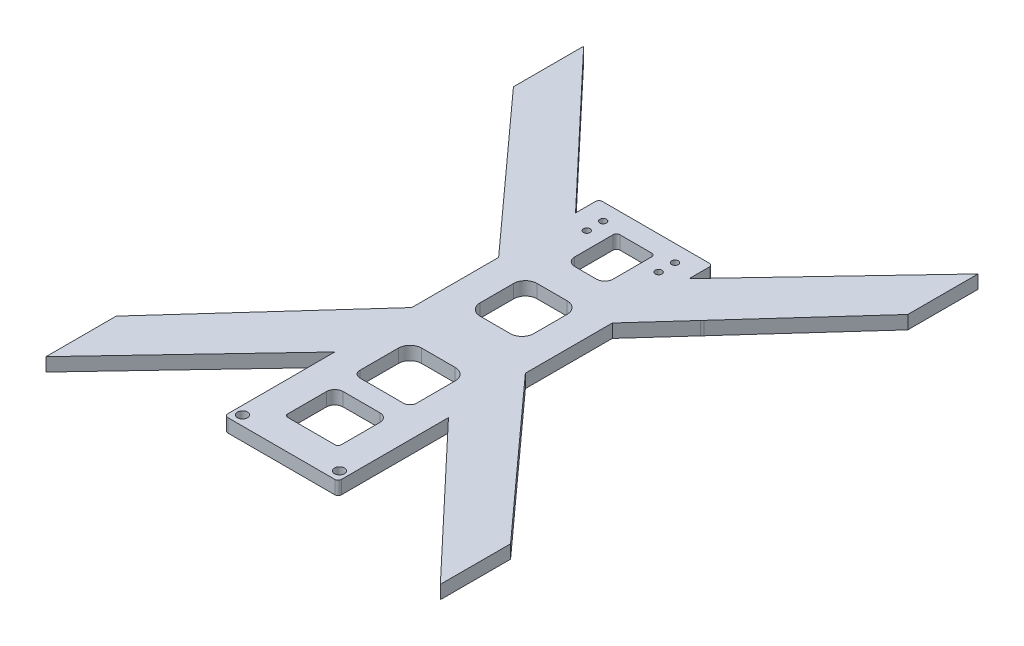
SolidWorks part; units mm, degrees
ref_plane "Front Plane" through (0, 0, 0) normal (0, 0, 1) x (1, 0, 0)
ref_plane "Top Plane" through (0, 0, 0) normal (0, 1, 0) x (1, 0, 0)
ref_plane "Right Plane" through (0, 0, 0) normal (1, 0, 0) x (0, 0, -1)
sketch "Frame Sketch" plane through (0, 0, 0) normal (0, 1, 0) x (1, 0, 0)
  line L0 (6.2981, 0.1404) -> (6.2981, 126.6085) construction
  line L6 (-48.6747, 0) -> (67.0859, 0) construction
  line L11 (6.2981, 0.1404) -> (6.2981, -105.8001) construction
  line L23 (-9.7019, 56.1404) -> (22.2981, 56.1404)
  line L24 (-10.7019, 55.1404) -> (-10.7019, -54.8596)
  line L25 (-9.7019, -55.8596) -> (22.2981, -55.8596)
  line L26 (23.2981, 55.1404) -> (23.2981, -54.8596)
  line L27 (-10.7019, 56.1404) -> (23.2981, -55.8596) construction
  line L28 (-10.7019, -55.8596) -> (23.2981, 56.1404) construction
  line L34 (23.2981, -22.8596) -> (65.2709, -67.262)
  line L37 (65.2709, -46.262) -> (65.2709, -67.262)
  line L38 (23.2981, 0.1404) -> (65.2709, -46.262)
  line L43 (23.2981, -22.8596) -> (23.2981, 0.1404)
  line L44 (-0.8423, -46.8596) -> (13.4385, -46.8596)
  line L45 (-1.7019, -46) -> (-1.7019, -34.3596)
  line L46 (0.7981, -31.8596) -> (11.7981, -31.8596)
  line L47 (14.2981, -46) -> (14.2981, -34.3596)
  line L48 (-1.7019, -46.8596) -> (14.2981, -31.8596) construction
  line L49 (-1.7019, -31.8596) -> (14.2981, -46.8596) construction
  line L50 (12.7981, -25.8596) -> (-0.2019, -25.8596)
  line L51 (14.7981, -23.8596) -> (14.7981, -12.3596)
  line L52 (11.2981, -8.8596) -> (1.2981, -8.8596)
  line L53 (-2.2019, -23.8596) -> (-2.2019, -12.3596)
  line L54 (14.7981, -25.8596) -> (-2.2019, -8.8596) construction
  line L55 (14.7981, -8.8596) -> (-2.2019, -25.8596) construction
  line L56 (1.7981, 8.1404) -> (10.7981, 8.1404)
  line L57 (-1.7019, 11.6404) -> (-1.7019, 21.6404)
  line L58 (1.7981, 25.1404) -> (10.7981, 25.1404)
  line L59 (14.2981, 11.6404) -> (14.2981, 21.6404)
  line L60 (-1.7019, 8.1404) -> (14.2981, 25.1404) construction
  line L61 (-1.7019, 25.1404) -> (14.2981, 8.1404) construction
  line L62 (3.0481, 35.1404) -> (9.5481, 35.1404)
  line L63 (0.5481, 37.6404) -> (0.5481, 49.1404)
  line L64 (1.5481, 50.1404) -> (11.0481, 50.1404)
  line L65 (12.0481, 37.6404) -> (12.0481, 49.1404)
  line L66 (0.5481, 35.1404) -> (12.0481, 50.1404) construction
  line L67 (0.5481, 50.1404) -> (12.0481, 35.1404) construction
  line L69 (23.2981, 49.1404) -> (65.2709, 93.5427)
  line L70 (23.2981, 26.1404) -> (65.2709, 72.5427)
  line L71 (65.2709, 72.5427) -> (65.2709, 93.5427)
  line L72 (23.2981, 26.1404) -> (23.2981, 49.1404)
  line L73 (-10.7019, 26.1404) -> (-52.6747, 72.5427)
  line L74 (-52.6747, 72.5427) -> (-52.6747, 93.5427)
  line L75 (-10.7019, 49.1404) -> (-52.6747, 93.5427)
  line L76 (-10.7019, 26.1404) -> (-10.7019, 49.1404)
  line L77 (-10.7019, -22.8596) -> (-52.6747, -67.262)
  line L78 (-52.6747, -46.262) -> (-52.6747, -67.262)
  line L79 (-10.7019, 0.1404) -> (-52.6747, -46.262)
  line L80 (-10.7019, -22.8596) -> (-10.7019, 0.1404)
  line L81 (-23.7019, 40.5123) -> (-10.7019, 26.1404)
  line L82 (-10.7019, 0.1404) -> (-23.7019, -14.2315)
  line L83 (-23.7019, 40.5123) -> (-10.7019, 26.1404)
  line L84 (-10.7019, 0.1404) -> (-23.7019, -14.2315)
  line L85 (-23.7019, 40.5123) -> (-10.7019, 26.1404)
  line L86 (-10.7019, 0.1404) -> (-23.7019, -14.2315)
  line L87 (-23.7019, 40.5123) -> (-10.7019, 26.1404)
  arc A8 (23.2981, 55.1404) -> (22.2981, 56.1404) centre (22.2981, 55.1404) ccw
  arc A9 (23.2981, -54.8596) -> (22.2981, -55.8596) centre (22.2981, -54.8596) cw
  arc A10 (-9.7019, 56.1404) -> (-10.7019, 55.1404) centre (-9.7019, 55.1404) ccw
  arc A11 (-9.7019, -55.8596) -> (-10.7019, -54.8596) centre (-9.7019, -54.8596) cw
  circle A12 centre (-8.2019, -52.9596) radius 1.5
  circle A13 centre (20.7981, -52.9596) radius 1.5
  arc A14 (14.2981, -46) -> (13.4385, -46.8596) centre (13.4385, -46) cw
  arc A15 (-0.8423, -46.8596) -> (-1.7019, -46) centre (-0.8423, -46) cw
  arc A16 (-1.7019, -34.3596) -> (0.7981, -31.8596) centre (0.7981, -34.3596) cw
  arc A17 (11.7981, -31.8596) -> (14.2981, -34.3596) centre (11.7981, -34.3596) cw
  arc A18 (14.7981, -23.8596) -> (12.7981, -25.8596) centre (12.7981, -23.8596) cw
  arc A19 (-2.2019, -23.8596) -> (-0.2019, -25.8596) centre (-0.2019, -23.8596) ccw
  arc A20 (14.7981, -12.3596) -> (11.2981, -8.8596) centre (11.2981, -12.3596) ccw
  arc A21 (1.2981, -8.8596) -> (-2.2019, -12.3596) centre (1.2981, -12.3596) ccw
  arc A22 (1.7981, 8.1404) -> (-1.7019, 11.6404) centre (1.7981, 11.6404) cw
  arc A23 (14.2981, 11.6404) -> (10.7981, 8.1404) centre (10.7981, 11.6404) cw
  arc A24 (1.7981, 25.1404) -> (-1.7019, 21.6404) centre (1.7981, 21.6404) ccw
  arc A25 (14.2981, 21.6404) -> (10.7981, 25.1404) centre (10.7981, 21.6404) ccw
  arc A26 (3.0481, 35.1404) -> (0.5481, 37.6404) centre (3.0481, 37.6404) cw
  arc A27 (12.0481, 37.6404) -> (9.5481, 35.1404) centre (9.5481, 37.6404) cw
  arc A28 (1.5481, 50.1404) -> (0.5481, 49.1404) centre (1.5481, 49.1404) ccw
  arc A29 (12.0481, 49.1404) -> (11.0481, 50.1404) centre (11.0481, 49.1404) ccw
  circle A30 centre (17.0481, 51.1404) radius 1
  circle A31 centre (17.0481, 46.2404) radius 1
  circle A32 centre (-4.4519, 51.1404) radius 1
  circle A33 centre (-4.4519, 46.2404) radius 1
  spline S0 degree 3 poles (-23.7019, 40.5123) (-9.7905, 25.4071) (-9.7035, 0.8596) (-23.7019, -14.2315) knots 0 0 0 0 1 1 1 1
  spline S1 degree 3 poles (36.2981, 40.5123) (22.3867, 25.4071) (22.2997, 0.8596) (36.2981, -14.2315) knots 0 0 0 0 1 1 1 1
  point P0 (0, 0)
  point P6 (0, 0)
  point P52 (6.2981, -39.3596)
  point P69 (6.2981, -17.3596)
  point P86 (6.2981, 16.6404)
  point P103 (6.2981, 42.6404)
  dimension "D6" = 1
  dimension "D7" = 2.9
  dimension "D8" = 2.5
  dimension "D5" = 17
  dimension "D11" = 9
  dimension "D12" = 9
  dimension "D13" = 10
  dimension "D14" = 33
  dimension "D17" = 23
  dimension "D18" = 21
  dimension "D19" = 26
  dimension "D20" = 7
  dimension "D23" = 23
  dimension "D24" = 21
  dimension "D25" = 1
  dimension "D26" = 1
  dimension "D30" = 5
  dimension "D31" = 5
  dimension "D32" = 4.9
  dimension "D33" = 6
  dimension "D34" = 5
  dimension "D3" = 112
  dimension "D4" = 34
  dimension "D9" = 15
  dimension "D10" = 16
  dimension "D15" = 17
  dimension "D16" = 6
  dimension "D21" = 17
  dimension "D22" = 16
  dimension "D27" = 17
  dimension "D28" = 15
  dimension "D29" = 11.5
  dimension "D35" = 13
extrude "Frame Bottom Plate" add sketch "Frame Sketch" along normal blind 4 contours L26 L23 L24 L25 | L37 | L70 L71 L69 L26 | L24 L79 L78 L77 | L34 L37 L38 L43 | L73 L74 L75 L76 region at (6.2981, 0, -1.1832) region at (43.9665, 0, -59.9976) region at (-31.3704, 0, 33.7169)
